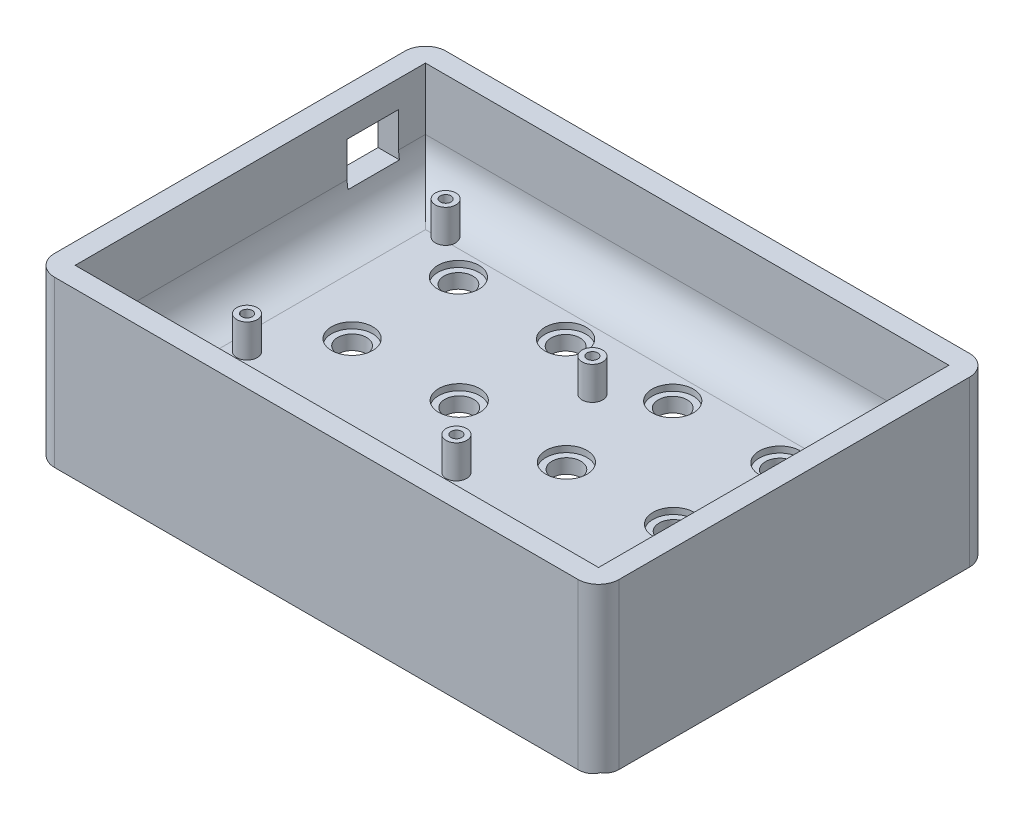
SolidWorks part; units mm, degrees
ref_plane "Front Plane" through (0, 0, 0) normal (0, 0, 1) x (1, 0, 0)
ref_plane "Top Plane" through (0, 0, 0) normal (0, 1, 0) x (1, 0, 0)
ref_plane "Right Plane" through (0, 0, 0) normal (1, 0, 0) x (0, 0, -1)
sketch "Sketch1" plane through (0, 0, 0) normal (0, 1, 0) x (1, 0, 0)
  line L1 (-64.25, -42.7816) -> (64.25, -42.7816)
  line L2 (-64.25, -42.7816) -> (-64.25, 42.7816)
  line L3 (-64.25, 42.7816) -> (64.25, 42.7816)
  line L4 (64.25, -42.7816) -> (64.25, 42.7816)
  line L5 (-64.25, -42.7816) -> (64.25, 42.7816) construction
  line L6 (-64.25, 42.7816) -> (64.25, -42.7816) construction
  line L7 (-68.5, -47.5) -> (68.5, -47.5)
  line L8 (-68.5, -47.5) -> (-68.5, 47.5)
  line L9 (-68.5, 47.5) -> (68.5, 47.5)
  line L10 (68.5, -47.5) -> (68.5, 47.5)
  line L11 (-68.5, -47.5) -> (68.5, 47.5) construction
  line L12 (-68.5, 47.5) -> (68.5, -47.5) construction
  point P0 (0, 0)
  point P6 (0, 0)
extrude "Boss-Extrude1" add sketch "Sketch1" along normal blind 10
sketch "Sketch2" plane through (0, 10, 0) normal (0, 1, 0) x (1, 0, 0)
  line L1 (-68.5, 47.5) -> (68.5, 47.5)
  line L2 (-68.5, 47.5) -> (-68.5, -47.5)
  line L3 (-68.5, -47.5) -> (68.5, -47.5)
  line L4 (68.5, 47.5) -> (68.5, -47.5)
extrude "Boss-Extrude2" add sketch "Sketch2" along normal blind 30
shell "Shell1" thickness 5 removed face at (0, 40, 0)
sketch "Sketch3" plane through (0, 15, 0) normal (0, 1, 0) x (1, 0, 0)
  circle A0 centre (-39.5, 26.5) radius 5
  circle A1 centre (-13.5, 26.5) radius 5
  circle A2 centre (38.5, 26.5) radius 5
  circle A3 centre (-39.5, 0.7005) radius 5
  circle A4 centre (-13.5, 0.7005) radius 5
  circle A5 centre (12.5, 26.5) radius 5
  circle A6 centre (12.5, 0.7005) radius 5
  circle A7 centre (38.5, 0.7005) radius 5
  circle A8 centre (-39.5, -25.2995) radius 5
  circle A9 centre (-13.5, -25.2995) radius 5
  circle A10 centre (12.5, -25.2995) radius 5
  circle A11 centre (38.5, -25.2995) radius 4.75
extrude "Cut-Extrude1" cut sketch "Sketch3" against normal blind 1.5
sketch "Sketch5" plane through (0, 13.5, 0) normal (0, 1, 0) x (1, 0, 0)
  circle A0 centre (-39.5, 26.5) radius 3.5
  circle A1 centre (12.5, -25.2995) radius 3.5
  circle A2 centre (12.5, 26.5) radius 3.5
  circle A3 centre (-13.5, 0.7005) radius 3.5
  circle A4 centre (12.5, 0.7005) radius 3.5
  circle A5 centre (38.5, 26.5) radius 3.5
  circle A6 centre (38.5, 0.7005) radius 3.5
  circle A7 centre (-39.5, 0.7005) radius 3.5
  circle A8 centre (-39.5, -25.2995) radius 3.5
  circle A9 centre (38.5, -25.2995) radius 3.5
  circle A11 centre (-13.5, 26.5) radius 3.5
  circle A12 centre (-13.5, -25.2995) radius 3.5
extrude "Cut-Extrude2" cut sketch "Sketch5" against normal up to next
sketch "Sketch7" plane through (0, 15, 0) normal (0, 1, 0) x (1, 0, 0)
  line L0 (-63.5, 42.5) -> (-63.5, -42.5) construction
  line L1 (-63.5, 36.0044) -> (5.1, 36.0044)
  line L2 (-63.5, 36.0044) -> (-63.5, -17.2956)
  line L3 (-63.5, -17.2956) -> (5.1, -17.2956)
  line L4 (5.1, 36.0044) -> (5.1, -17.2956)
  line L5 (-63.5, 36.0044) -> (-49.5, 36.0044)
  line L6 (-49.5, -14.7956) -> (-49.5, 33.4044)
  line L7 (-49.5, -17.2956) -> (-49.5, -14.7956)
  line L8 (-49.5, 33.4044) -> (1.3, 33.4044)
  line L9 (1.3, 33.4044) -> (1.3, 18.2044)
  line L10 (1.3, 18.2044) -> (1.3, -14.7956)
  circle A0 centre (-49.5, 33.4044) radius 1.3
  circle A1 centre (-49.5, 33.4044) radius 2.5
  circle A2 centre (-49.5, -14.7956) radius 1.3
  circle A3 centre (-49.5, -14.7956) radius 2.5
  circle A4 centre (1.3, 18.2044) radius 1.3
  circle A5 centre (1.3, -14.7956) radius 1.3
  circle A6 centre (1.3, 18.2044) radius 2.5
  circle A7 centre (1.3, -14.7956) radius 2.5
extrude "Boss-Extrude5" add sketch "Sketch7" along normal blind 8 contours A3 | A2 | A0 | A1 | A4 | A6 | A5 | A7
sketch "Sketch9" plane through (-63.5, 0, 0) normal (1, 0, 0) x (0, 0, -1)
  line L0 (42.5, 15) -> (36, 15)
  line L1 (42.5, 15) -> (-42.5, 15) construction
  line L2 (36, 15) -> (36, 23)
  line L4 (36, 23) -> (23.5, 23)
  line L5 (36, 23) -> (36, 33.5)
  line L6 (36, 33.5) -> (23.5, 33.5)
  line L7 (23.5, 23) -> (23.5, 33.5)
extrude "Cut-Extrude3" cut sketch "Sketch9" against normal blind 8 contours L7 L4 L5 L6 region at (-63.5, 28.25, -29.75)
fillet "Fillet1" radius 5 8 edges at (-68.5, 20, -47.5) (68.5, 20, -47.5) (68.5, 20, 47.5) (-68.5, 20, 47.5) (0, 0, -42.7816) (64.25, 0, 0) (0, 0, 42.7816) (-64.25, 0, 0)
fillet "Fillet2" radius 10 4 edges at (63.5, 15, 0) (0, 15, -42.5) (-63.5, 15, 0) (0, 15, 42.5)
